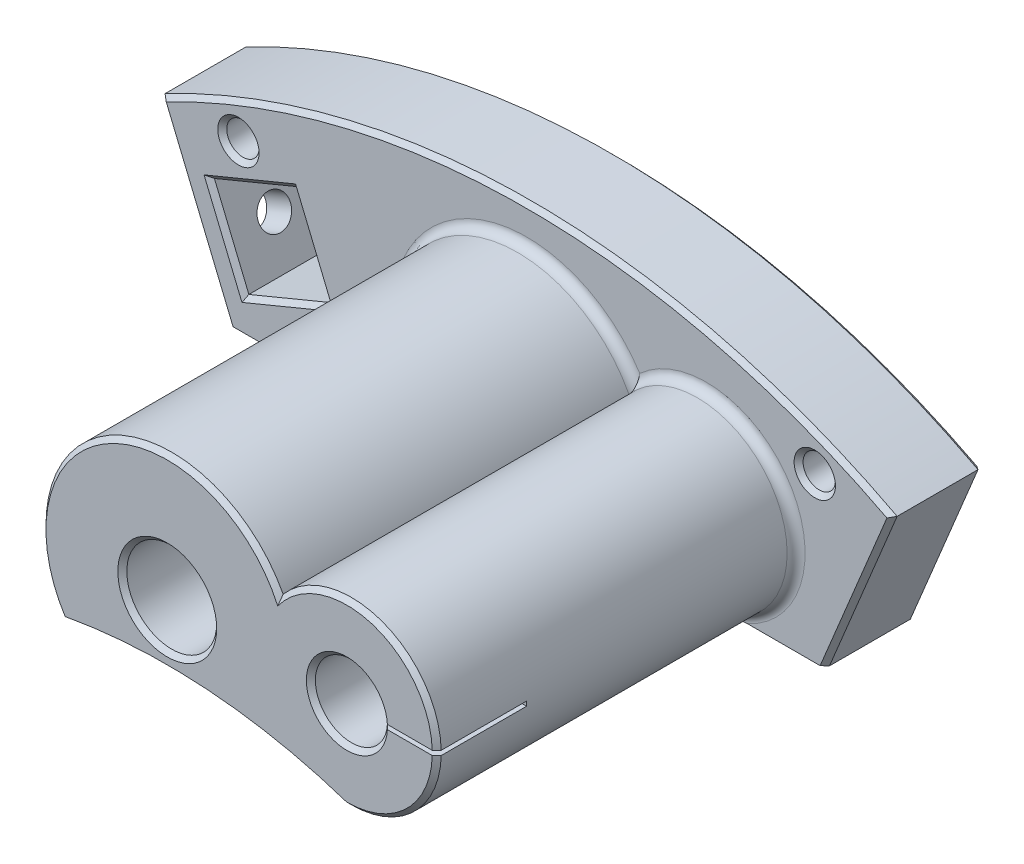
SolidWorks part; units mm, degrees
ref_plane "Front Plane" through (0, 0, 0) normal (0, 0, 1) x (1, 0, 0)
ref_plane "Top Plane" through (0, 0, 0) normal (0, 1, 0) x (1, 0, 0)
ref_plane "Right Plane" through (0, 0, 0) normal (1, 0, 0) x (0, 0, -1)
sketch "Sketch1" plane through (0, 0, 0) normal (0, 0, 1) x (1, 0, 0)
  line L0 (-46.9014, 0) -> (43.5211, 0) construction
  line L1 (0, 38.5211) -> (0, -80.4339) construction
  line L2 (-33.5349, -69.25) -> (36.7559, -69.25) construction
  line L3 (0, -69.25) -> (-37.9703, 22.4183) construction
  line L4 (-40.7467, 8.1836) -> (-33.2148, -10)
  line L5 (-25.9885, 6.5901) -> (-35.2504, 2.7537)
  line L6 (-35.2504, 2.7537) -> (-31.414, -6.5082)
  line L7 (-31.414, -6.5082) -> (-22.1521, -2.6718)
  line L8 (-22.1521, -2.6718) -> (-25.9885, 6.5901)
  line L11 (40.7467, 8.1836) -> (33.2148, -10)
  line L12 (20, 7.6656) -> (20, -13.8845) construction
  line L13 (-33.2148, -10) -> (33.2148, -10)
  circle A1 centre (-28.7013, 0.041) radius 5.0125 construction
  arc A2 (40.7467, 8.1836) -> (-40.7467, 8.1836) centre (0, -69.25) ccw
  circle A6 centre (0, 0) radius 5
  circle A7 centre (-32.0765, 8.1894) radius 1.8
  circle A8 centre (32.0765, 8.1894) radius 1.8
  circle A9 centre (20, 0) radius 3
  dimension "D2" = 20
  dimension "D7" = 75
  dimension "D8" = 175
  dimension "D9" = 3
  dimension "D12" = 10
  dimension "D13" = 3.6
  dimension "D14" = 32.0765
  dimension "D16" = 6
  dimension "D3" = 69.25
  dimension "D4" = 22.5
  dimension "D5" = 10.025
  dimension "D6" = 90
extrude "Boss-Extrude1" add sketch "Sketch1" along normal blind 10
sketch "Sketch3" plane through (0, 0, 0) normal (0, 0, -1) x (-1, 0, 0)
  circle A0 centre (0, 0) radius 11.025
  dimension "D1" = 22.05
sketch "Sketch4" plane through (0, 0, 0) normal (0, 0, -1) x (-1, 0, 0)
  circle A0 centre (0, 0) radius 12.525
  dimension "D1" = 25.05
sketch "Sketch5" plane through (-29.1145, -12.0596, 0) normal (0.9239, 0.3827, 0) x (0, 0, -1)
  line L5 (-10, 16.0338) -> (0, 16.0338) construction
  line L6 (0, 16.0338) -> (0, 6.0088) construction
  circle A0 centre (-4.75, 11.0188) radius 1.8
  dimension "D1" = 3.6
  dimension "D2" = 5.015
  dimension "D3" = 4.75
extrude "Cut-Extrude4" cut sketch "Sketch5" against normal blind 10
sketch "Sketch6" plane through (0, 0, 10) normal (0, 0, 1) x (1, 0, 0)
  line L0 (9.798, -10) -> (-9.798, -10)
  line L1 (9.798, -10) -> (20, -10)
  line L2 (0, 22.1581) -> (0, -16.2187) construction
  line L3 (-33.2148, -10) -> (33.2148, -10) construction
  arc A2 (12.4, 6.4992) -> (-9.798, -10) centre (0, 0) ccw
  arc A3 (20, -10) -> (12.4, 6.4992) centre (20, 0) ccw
  circle A4 centre (0, 0) radius 5 construction
  circle A5 centre (0, 0) radius 5
  circle A6 centre (20, 0) radius 3 construction
  circle A7 centre (20, 0) radius 3
  dimension "D1" = 28
  dimension "D2" = 20
  dimension "D3" = 20
extrude "Boss-Extrude3" add sketch "Sketch6" along normal blind 40
sketch "Sketch7" plane through (0, 0, 50) normal (0, 0, 1) x (1, 0, 0)
  circle A0 centre (0, 0) radius 11.025
  dimension "D1" = 22.05
sketch "Sketch8" plane through (0, 0, 50) normal (0, 0, 1) x (1, 0, 0)
  circle A0 centre (0, 0) radius 12.525
  dimension "D1" = 25.05
sketch "Sketch9" plane through (0, 0, 50) normal (0, 0, 1) x (1, 0, 0)
  line L0 (-15.573, 0) -> (48.0602, 0) construction
  line L1 (24.0047, 0.25) -> (29.9969, 0.25)
  line L2 (24.0047, -0.25) -> (29.9969, -0.25)
  arc A0 (24.0047, 0.25) -> (24.0047, -0.25) centre (20, 0) ccw
  arc A1 (20, -10) -> (12.4, 6.4992) centre (20, 0) ccw construction
  arc A2 (29.9969, -0.25) -> (29.9969, 0.25) centre (20, 0) ccw
  dimension "D1" = 8.025
  dimension "D2" = 0.25
extrude "Cut-Extrude7" cut sketch "Sketch9" against normal blind 10
chamfer "Chamfer1" distance 0.5 15 edges at (30.2765, 8.1894, 10) (-33.3322, -1.8772, 10) (-26.7831, -4.59, 10) (-24.0703, 1.9592, 10) (-30.6195, 4.6719, 10) (-30.2765, 8.1894, 10) (36.9808, -0.9082, 10) (0, 18.25, 10) (-36.9808, -0.9082, 10) (15.9875, 0, 50) (26.9821, -7.1589, 50) (5.101, -10, 50) (23.3466, 9.4234, 50) (-8.3516, 11.2362, 50) (5, 0, 50)
fillet "Fillet1" radius 1 2 edges at (29.0827, 4.1838, 10) (-8.3516, 11.2362, 10)
sketch "Sketch10" plane through (0, 0, 0) normal (0, 0, -1) x (-1, 0, 0)
  circle A2 centre (-20, 0) radius 3 construction
  circle A3 centre (-20, 0) radius 3
extrude "Boss-Extrude4" add sketch "Sketch10" against normal blind 40
chamfer "Chamfer2" distance 0.5 angle 45 11 edges at (30.2765, 8.1894, 0) (-30.2765, 8.1894, 0) (-26.7831, -4.59, 0) (-33.3322, -1.8772, 0) (-30.6195, 4.6719, 0) (-24.0703, 1.9592, 0) (0, 18.25, 0) (-36.9808, -0.9082, 0) (36.9808, -0.9082, 0) (5, 0, 0) (0, -10, 0)
sketch "Sketch12" plane through (0, 0, 0) normal (0, 0, 1) x (1, 0, 0)
  line L0 (0, 27.2627) -> (0, -82.8876) construction
  line L1 (-59.9971, -69.25) -> (62.3114, -69.25) construction
  circle A0 centre (0, -69.25) radius 63
  dimension "D2" = 126
  dimension "D3" = 69.25
  dimension "D1" = 69.25
extrude "Cut-Extrude8" cut sketch "Sketch12" along normal through all
